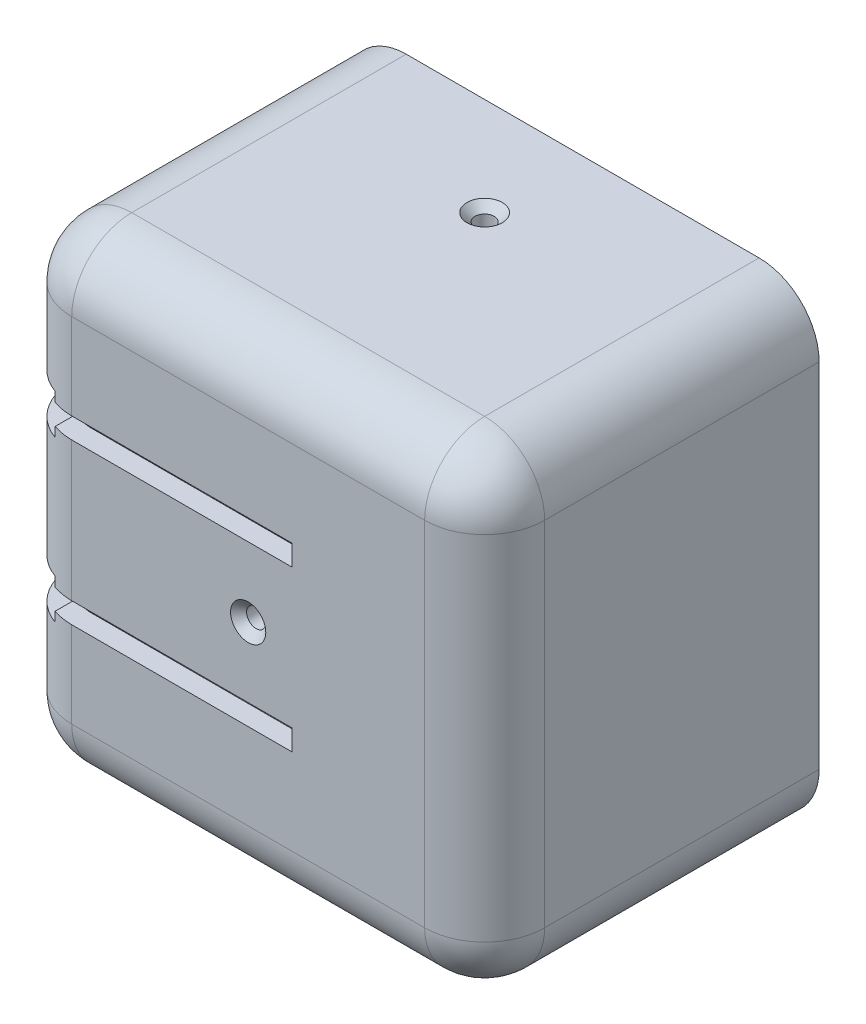
SolidWorks part; units mm, degrees
note: '?' marks a value the reader was unsure of.
ref_plane "Front Plane" through (0, 0, 0) normal (0, 0, 1) x (1, 0, 0)
ref_plane "Top Plane" through (0, 0, 0) normal (0, 1, 0) x (1, 0, 0)
ref_plane "Right Plane" through (0, 0, 0) normal (1, 0, 0) x (0, 0, -1)
sketch "Sketch1" plane through (0, 0, 0) normal (0, 0, 1) x (1, 0, 0)
  line L0 (0, 78.4471) -> (0, -76.9705) construction
  line L1 (-83.0616, 0) -> (77.155, 0) construction
  line L3 (-29.55, 29.55) -> (29.55, 29.55)
  line L4 (-29.55, 29.55) -> (-29.55, -29.55)
  line L5 (-29.55, -29.55) -> (29.55, -29.55)
  line L6 (29.55, 29.55) -> (29.55, -29.55)
  dimension "D1" = 59.1
  dimension "D2" = 59.1
extrude "Boss-Extrude1" add sketch "Sketch1" along normal blind 59.1
ref_plane "Plane9" through (0, 0, 29.55) normal (0, 0, 1) x (1, 0, 0)
ref_plane "Plane1" through (0, -14.775, 14.775) normal (0, -0.7071, 0.7071) x (1, 0, 0)
ref_axis "Axis1" through (-29.55, 29.55, 59.1) along (0.5774, -0.5774, -0.5774)?
ref_plane "Plane2" through (0, 0, 0) normal (-0.5774, -0.5774, 0.5774) x (0.8165, -0.4082, 0.4082)
ref_plane "Plane3" through (-19.7, -19.7, 19.7) normal (0.5774, 0.5774, -0.5774) x (-0.8165, 0.4082, -0.4082)
ref_plane "Plane4" through (-9.85, -9.85, 9.85) normal (-0.5774, -0.5774, 0.5774) x (0.8165, -0.4082, 0.4082)
ref_plane "Plane6" through (0, 0, 29.55) normal (0, 0, -1) x (-1, 0, 0)
ref_plane "Plane10" through (0, 0, 29.55) normal (0, 0, -1) x (-1, 0, 0)
ref_plane "Plane11" through (0, 0, 19.55) normal (0, 0, -1) x (-1, 0, 0)
sketch "Sketch2" plane through (-13.4004, -13.4004, 19.55) normal (0, 0, 1) x (0.9659, -0.2588, 0)
  line L1 (73.4206, 63.196) -> (-42.9368, 63.196)
  line L2 (73.4206, 63.196) -> (73.4206, -31.2358)
  line L3 (73.4206, -31.2358) -> (-42.9368, -31.2358)
  line L4 (-42.9368, 63.196) -> (-42.9368, -31.2358)
extrude "Cut-Extrude1" cut sketch "Sketch2" against normal through all from offset 2.25 offset against normal yes
ref_plane "Plane5" through (-39.4, -39.4, 39.4) normal (-0.5774, -0.5774, 0.5774) x (-0.8165, 0.4082, -0.4082)
fillet "Fillet1" radius 7.5 8 edges at (0, -29.55, 59.1) (29.55, 0, 59.1) (29.55, -29.55, 38.2) (-29.55, -29.55, 38.2) (-29.55, 0, 59.1) (0, 29.55, 59.1) (-29.55, 29.55, 38.2) (29.55, 29.55, 38.2)
shell "Shell1" thickness 2.5
ref_plane "Plane7" through (-9.8314, 1.2497, 53.5942) normal (0.4082, -0.8165, -0.4082) x (-0.9129, -0.3651, -0.1826)
sketch "Sketch14" plane through (0, 0, 59.1) normal (0, 0, 1) x (1, 0, 0)
  line L0 (-29.55, -8.7) -> (-27.05, -8.7)
  line L1 (-27.05, -8.7) -> (-27.05, -7.5)
  line L2 (-27.05, -7.5) -> (-24.55, -7.5)
  line L3 (-24.55, -7.5) -> (-24.55, -12.5)
  line L4 (-24.55, -12.5) -> (-27.05, -12.5)
  line L5 (-27.05, -12.5) -> (-27.05, -11.3)
  line L6 (-27.05, -11.3) -> (-29.55, -11.3)
  line L7 (-29.55, -11.3) -> (-29.55, -8.7)
  line L8 (-29.55, -22.05) -> (-29.55, 22.05) construction
  line L9 (-42.181, -10) -> (-13.3805, -10) construction
  line L10 (-43.1184, 0) -> (38.5678, 0) construction
  line L11 (-29.55, 11.3) -> (-29.55, 8.7)
  line L12 (-27.05, 11.3) -> (-29.55, 11.3)
  line L13 (-27.05, 12.5) -> (-27.05, 11.3)
  line L14 (-24.55, 12.5) -> (-27.05, 12.5)
  line L15 (-24.55, 7.5) -> (-24.55, 12.5)
  line L16 (-27.05, 7.5) -> (-24.55, 7.5)
  line L17 (-27.05, 8.7) -> (-27.05, 7.5)
  line L18 (-29.55, 8.7) -> (-27.05, 8.7)
  dimension "D1" = 2.6
  dimension "D2" = 5
  dimension "D3" = 2.5
  dimension "D4" = 2.5
  dimension "D5" = 10
extrude "Cut-Extrude7" cut sketch "Sketch14" against normal blind 35
sketch "Sketch15" plane through (-29.55, 0, -29.55) normal (1, 0, 0) x (0, 0, -1)
  line L0 (-88.65, -8.7) -> (-86.05, -8.7)
  line L1 (-86.05, -8.7) -> (-86.05, -7.5)
  line L2 (-86.05, -7.5) -> (-83.45, -7.5)
  line L3 (-83.45, -7.5) -> (-83.45, -12.5)
  line L4 (-83.45, -12.5) -> (-86.05, -12.5)
  line L5 (-86.05, -12.5) -> (-86.05, -11.3)
  line L6 (-86.05, -11.3) -> (-88.65, -11.3)
  line L7 (-88.65, -11.3) -> (-88.65, -8.7)
  line L9 (-104.5918, -10) -> (-13.3805, -10) construction
  line L10 (-98.8039, 0) -> (-26.2859, 0) construction
  line L11 (-88.65, 11.3) -> (-88.65, 8.7)
  line L12 (-86.05, 11.3) -> (-88.65, 11.3)
  line L13 (-86.05, 12.5) -> (-86.05, 11.3)
  line L14 (-83.45, 12.5) -> (-86.05, 12.5)
  line L15 (-83.45, 7.5) -> (-83.45, 12.5)
  line L16 (-86.05, 7.5) -> (-83.45, 7.5)
  line L17 (-86.05, 8.7) -> (-86.05, 7.5)
  line L18 (-88.65, 8.7) -> (-86.05, 8.7)
  line L19 (-88.65, 22.05) -> (-88.65, -22.05) construction
  line L20 (2.955, 0) -> (-62.055, 0) construction
  dimension "D1" = 2.6
  dimension "D2" = 5
  dimension "D3" = 2.6
  dimension "D4" = 2.6
  dimension "D5" = 10
extrude "Cut-Extrude8" cut sketch "Sketch15" along normal blind 35
sketch "Sketch16" plane through (-27.05, 0, 0) normal (1, 0, 0) x (0, 0, -1)
  line L0 (-57.1902, 12.5) -> (-57.1902, 11.3) construction
  line L1 (-56.5, -12.5) -> (-57.1902, -12.5)
  line L2 (-56.5, -12.5) -> (-56.5, -7.5)
  line L3 (-56.5, -7.5) -> (-57.1902, -7.5)
  line L4 (-57.1902, -12.5) -> (-57.1902, -7.5)
  line L5 (-56.5, 7.5) -> (-57.1902, 7.5)
  line L6 (-56.5, 7.5) -> (-56.5, 12.5)
  line L7 (-56.5, 12.5) -> (-57.1902, 12.5)
  line L8 (-57.1902, 7.5) -> (-57.1902, 12.5)
  line L9 (-56.5, 12.5) -> (-57.1902, 12.5) construction
extrude "Cut-Extrude9" cut sketch "Sketch16" against normal through all
sketch "Sketch18" plane through (0, -27.05, 0) normal (0, 1, 0) x (1, 0, 0)
  circle A0 centre (-22.05, -51.6) radius 5
  dimension "D1" = 10
extrude "Boss-Extrude2" add sketch "Sketch18" along normal blind 3
sketch "Sketch17" plane through (0, -29.55, 0) normal (0, -1, 0) x (1, 0, 0)
  circle A0 centre (-22.05, 51.6) radius 1.5
  dimension "D1" = 3
extrude "Cut-Extrude10" cut sketch "Sketch17" against normal blind 10
ref_plane "Plane8" through (0, -6.5, 0) normal (0, -1, 0) x (-1, 0, 0)
ref_axis "Axis2" through (-22.05, -24.05, 51.6) along (0, -1, 0)?
sketch "Sketch20" plane through (0, -29.55, 0) normal (0, -1, 0) x (1, 0, 0)
  line L0 (-36.3458, 37.3042) -> (-9.0033, 64.6467) construction
  line L1 (22.05, 51.6) -> (-20.55, 51.6) construction
  line L2 (-34.1921, 63.7421) -> (-5.1828, 34.7328) construction
  line L3 (-22.6479, 52.9757) -> (-23.0721, 53.4)
  line L4 (-23.0721, 53.4) -> (-23.85, 52.6221)
  line L5 (-23.85, 52.6221) -> (-23.4257, 52.1979)
  line L6 (-21.0279, 49.8) -> (-21.4521, 50.2243)
  line L7 (-20.25, 50.5779) -> (-21.0279, 49.8)
  line L8 (-20.6743, 51.0021) -> (-20.25, 50.5779)
  arc A0 (-22.6479, 52.9757) -> (-23.4257, 52.1979) centre (-22.05, 51.6) ccw
  arc A1 (-20.6743, 51.0021) -> (-21.4521, 50.2243) centre (-22.05, 51.6) cw
  point P9 (-22.86, 53.1878)
  dimension "D2" = 3
  dimension "D1" = 45
  dimension "D3" = 1.1
  dimension "D4" = 0.6
extrude "Cut-Extrude11" cut sketch "Sketch20" against normal up to next
hole_wizard "CSK SLOT for M2 Countersunk Flat Head Screw1" positions "Sketch21" profile "Sketch22" size "M2" standard "ISO" slot yes end condition through all
sketch "Sketch21" plane through (0, 29.55, 0) normal (0, -1, 0) x (0, 0, 1)
  line L2 (-23.1275, 0) -> (23.1275, 0) construction
  line L3 (29.55, 24.2) -> (29.55, -24.2) construction
  point P0 (29.55, 0)
sketch "Sketch22" plane through (0, 29.55, 29.55) normal (1, 0, 0) x (0, 0, 1)
  line L0 (0, 0) -> (0, 59.1)
  line L1 (0, 59.1) -> (1.2, 59.1)
  line L2 (1.2, 59.1) -> (1.2, 1)
  line L3 (1.2, 1) -> (2.2, 0)
  line L5 (2.2, 0) -> (0, 0)
  line L6 (-1.2, 1) -> (-2.2, 0) construction
  line L11 (0, -6.35) -> (0, 107.95) construction
  dimension "Thru Hole Dia." = 2.4
  dimension "Thru Hole Depth" = 59.1
  dimension "Near C'Sink Dia." = 4.4
  dimension "Near C'Sink Angle" = 90
hole_wizard "CSK SLOT for M2 Countersunk Flat Head Screw2" positions "Sketch23" profile "Sketch24" size "M2" standard "ISO" slot yes end condition through all
sketch "Sketch23" plane through (0, 0, 59.1) normal (0, 0, 1) x (1, 0, 0)
  line L0 (23.1275, 0) -> (-23.1275, 0) construction
  line L2 (0, -23.1275) -> (0, 23.1275) construction
  point P0 (0, 0)
sketch "Sketch24" plane through (0, 0, 59.1) normal (1, 0, 0) x (0, -1, 0)
  line L0 (0, 0) -> (0, 41.8)
  line L1 (0, 41.8) -> (1.2, 41.8)
  line L2 (1.2, 41.8) -> (1.2, 1)
  line L3 (1.2, 1) -> (2.2, 0)
  line L5 (2.2, 0) -> (0, 0)
  line L6 (-1.2, 1) -> (-2.2, 0) construction
  line L11 (0, -6.35) -> (0, 107.95) construction
  dimension "Thru Hole Dia." = 2.4
  dimension "Thru Hole Depth" = 41.8
  dimension "Near C'Sink Dia." = 4.4
  dimension "Near C'Sink Angle" = 90
hole_wizard "CSK SLOT for M2 Countersunk Flat Head Screw3" positions "Sketch25" profile "Sketch26" size "M2" standard "ISO" slot yes end condition through all
sketch "Sketch25" plane through (0, -29.55, 0) normal (0, -1, 0) x (-1, 0, 0)
  line L2 (-32.505, -29.55) -> (32.505, -29.55) construction
  line L4 (0, 23.1275) -> (0, -23.1275) construction
  point P2 (0, -29.55)
sketch "Sketch26" plane through (0, -29.55, 29.55) normal (1, 0, 0) x (0, 0, -1)
  line L0 (0, 0) -> (0, 59.1)
  line L1 (0, 59.1) -> (1.2, 59.1)
  line L2 (1.2, 59.1) -> (1.2, 1)
  line L3 (1.2, 1) -> (2.2, 0)
  line L5 (2.2, 0) -> (0, 0)
  line L6 (-1.2, 1) -> (-2.2, 0) construction
  line L11 (0, -6.35) -> (0, 107.95) construction
  dimension "Thru Hole Dia." = 2.4
  dimension "Thru Hole Depth" = 59.1
  dimension "Near C'Sink Dia." = 4.4
  dimension "Near C'Sink Angle" = 90
sketch "Sketch27" plane through (-29.55, 29.55, 0) normal (1, 0, 0) x (0, 0, -1)
  line L0 (-18.3, -59.1) -> (-18.3, -61.7)
  line L1 (-18.3, -61.7) -> (-17.05, -61.7)
  line L2 (-17.05, -61.7) -> (-17.05, -64.2)
  line L3 (-17.05, -64.2) -> (-22.05, -64.2)
  line L4 (-22.05, -64.2) -> (-22.05, -61.7)
  line L5 (-22.05, -61.7) -> (-20.8, -61.7)
  line L6 (-20.8, -61.7) -> (-20.8, -59.1)
  line L7 (-20.8, -59.1) -> (-18.3, -59.1)
  line L8 (-19.55, -57.6612) -> (-19.55, 18.17) construction
  line L9 (-29.55, 2.955) -> (-29.55, -62.055) construction
  line L10 (-50.1, -59.1) -> (-17.3, -59.1) construction
  line L12 (-29.55, -57.6612) -> (-29.55, 18.17) construction
  line L13 (-38.3, -59.1) -> (-40.8, -59.1)
  line L14 (-38.3, -61.7) -> (-38.3, -59.1)
  line L15 (-37.05, -61.7) -> (-38.3, -61.7)
  line L16 (-37.05, -64.2) -> (-37.05, -61.7)
  line L17 (-42.05, -64.2) -> (-37.05, -64.2)
  line L18 (-42.05, -61.7) -> (-42.05, -64.2)
  line L19 (-40.8, -61.7) -> (-42.05, -61.7)
  line L20 (-40.8, -59.1) -> (-40.8, -61.7)
  point P10 (-22.05, -62.95)
  dimension "D1" = 2.5
  dimension "D2" = 5
  dimension "D3" = 2.6
  dimension "D4" = 2.5
  dimension "D5" = 10
extrude "Boss-Extrude3" add sketch "Sketch27" along normal blind 35
sketch "Sketch28" plane through (0, 0, 59.1) normal (0, 0, 1) x (1, 0, 0)
  line L0 (-29.55, -29.55) -> (-29.55, -32.15) construction
  line L1 (-22.05, -29.55) -> (-29.55, -29.55)
  line L2 (-22.05, -29.55) -> (-22.05, -34.65)
  line L3 (-22.05, -34.65) -> (-29.55, -34.65)
  line L4 (-29.55, -29.55) -> (-29.55, -34.65)
  line L5 (5.45, -34.65) -> (-29.55, -34.65) construction
extrude "Cut-Extrude12" cut sketch "Sketch28" against normal through all
